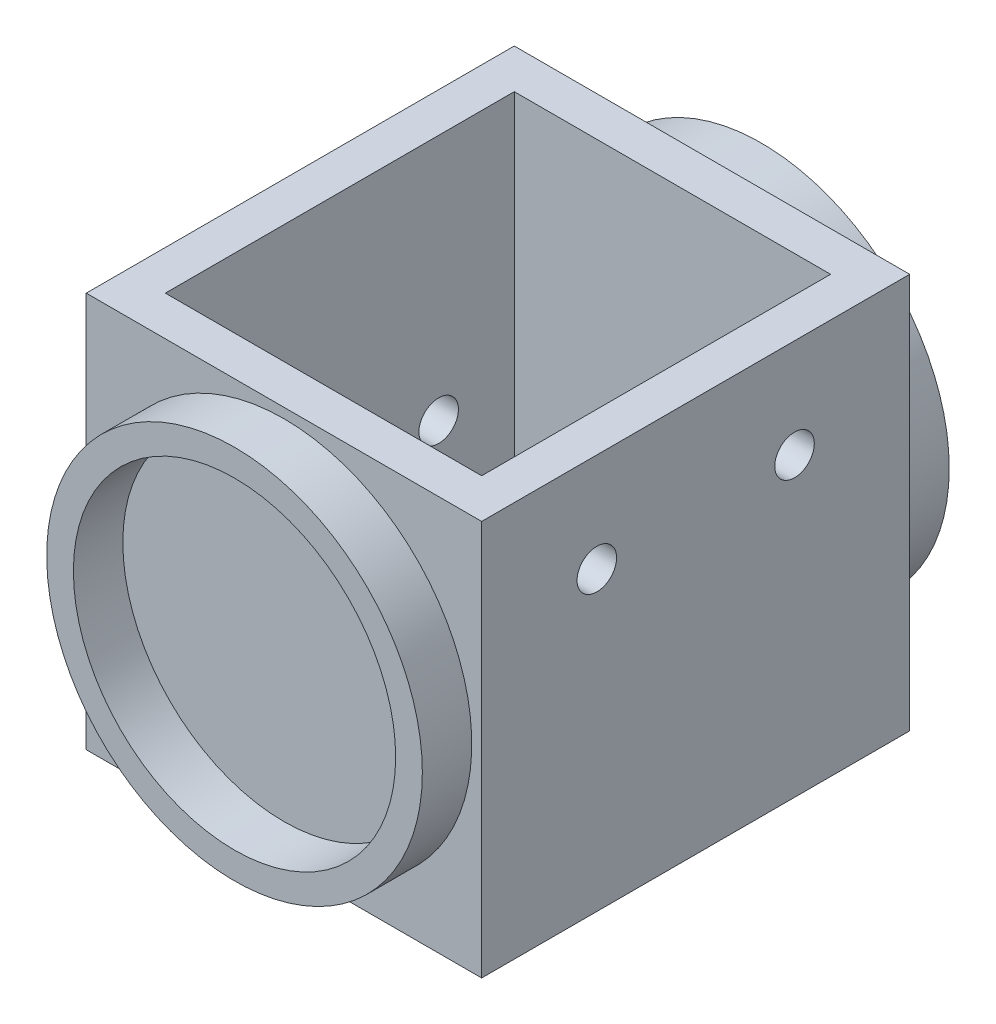
SolidWorks part; units mm, degrees
ref_plane "Front Plane" through (0, 0, 0) normal (0, 0, 1) x (1, 0, 0)
ref_plane "Top Plane" through (0, 0, 0) normal (0, 1, 0) x (1, 0, 0)
ref_plane "Right Plane" through (0, 0, 0) normal (1, 0, 0) x (0, 0, -1)
sketch "Sketch1" plane through (0, 0, 0) normal (0, 0, 1) x (1, 0, 0)
  line L1 (-25.4, 25.4) -> (25.4, 25.4)
  line L2 (-25.4, 25.4) -> (-25.4, -25.4)
  line L3 (-25.4, -25.4) -> (25.4, -25.4)
  line L4 (25.4, 25.4) -> (25.4, -25.4)
  point P4 (0, 25.4)
  point P6 (25.4, 0)
  dimension "D1" = 50.8
  dimension "D2" = 50.8
extrude "Boss-Extrude1" add sketch "Sketch1" along normal up to surface (54.991 mm away) contours L4 L3 L2 L1
sketch "Sketch2" plane through (0, 25.4, 0) normal (0, 1, 0) x (1, 0, 0)
  line L8 (-20.32, -49.911) -> (20.32, -49.911)
  line L9 (20.32, -49.911) -> (20.32, -5.08)
  line L10 (20.32, -5.08) -> (-20.32, -5.08)
  line L11 (-20.32, -5.08) -> (-20.32, -49.911)
  line L12 (-20.32, -49.911) -> (20.32, -49.911)
  line L13 (20.32, -49.911) -> (20.32, -5.08)
  line L14 (20.32, -5.08) -> (-20.32, -5.08)
  line L15 (-20.32, -5.08) -> (-20.32, -49.911)
  dimension "D1" = 5.08
extrude "Cut-Extrude1" cut sketch "Sketch2" against normal through all
sketch "Sketch3" plane through (0, 0, 54.991) normal (0, 0, 1) x (1, 0, 0)
  circle A0 centre (0, 0) radius 20.701
  circle A1 centre (0, 0) radius 24.13
  dimension "D1" = 41.402
  dimension "D2" = 48.26
extrude "Boss-Extrude2" add sketch "Sketch3" along normal blind 6.35
ref_plane "Plane1" through (0, 0, 27.4955) normal (0, 0, 1) x (1, 0, 0)
mirror "Mirror1" about plane through (0, 0, 27.4955) normal (0, 0, 1) of "Boss-Extrude2"
sketch "Sketch4" plane through (-25.4, 0, 0) normal (-1, 0, 0) x (0, 0, 1)
  line L0 (0, 25.4) -> (54.991, 25.4) construction
  line L1 (54.991, 25.4) -> (0, 25.4) construction
  line L2 (0, 25.4) -> (0, -25.4) construction
  line L3 (54.991, -25.4) -> (54.991, 25.4) construction
  line L4 (27.4955, 25.4) -> (27.4955, 2.664) construction
  line L5 (14.7955, -6.35) -> (40.1955, -6.35) construction
  circle A0 centre (14.7955, -6.35) radius 2.54
  circle A1 centre (40.1955, -6.35) radius 2.54
  point P14 (27.4955, -6.35)
  dimension "D1" = 5.08
  dimension "D2" = 5.08
  dimension "D3" = 25.4
  dimension "D4" = 31.75
extrude "Cut-Extrude2" cut sketch "Sketch4" against normal up to next
sketch "Sketch5" plane through (25.4, 0, 0) normal (1, 0, 0) x (0, 0, -1)
  line L0 (-54.991, -25.4) -> (0, -25.4) construction
  line L1 (-54.991, -25.4) -> (-54.991, 25.4) construction
  line L2 (-54.991, -25.4) -> (0, -25.4) construction
  line L3 (0, 25.4) -> (0, -25.4) construction
  line L4 (-27.4955, -25.4) -> (-27.4955, -1.804) construction
  line L5 (-40.1955, 12.7) -> (-14.7955, 12.7) construction
  circle A0 centre (-40.1955, 12.7) radius 2.54
  circle A1 centre (-14.7955, 12.7) radius 2.54
  point P14 (-27.4955, 12.7)
  dimension "D1" = 5.08
  dimension "D2" = 5.08
  dimension "D3" = 12.7
  dimension "D4" = 38.1
extrude "Cut-Extrude3" cut sketch "Sketch5" against normal up to next
